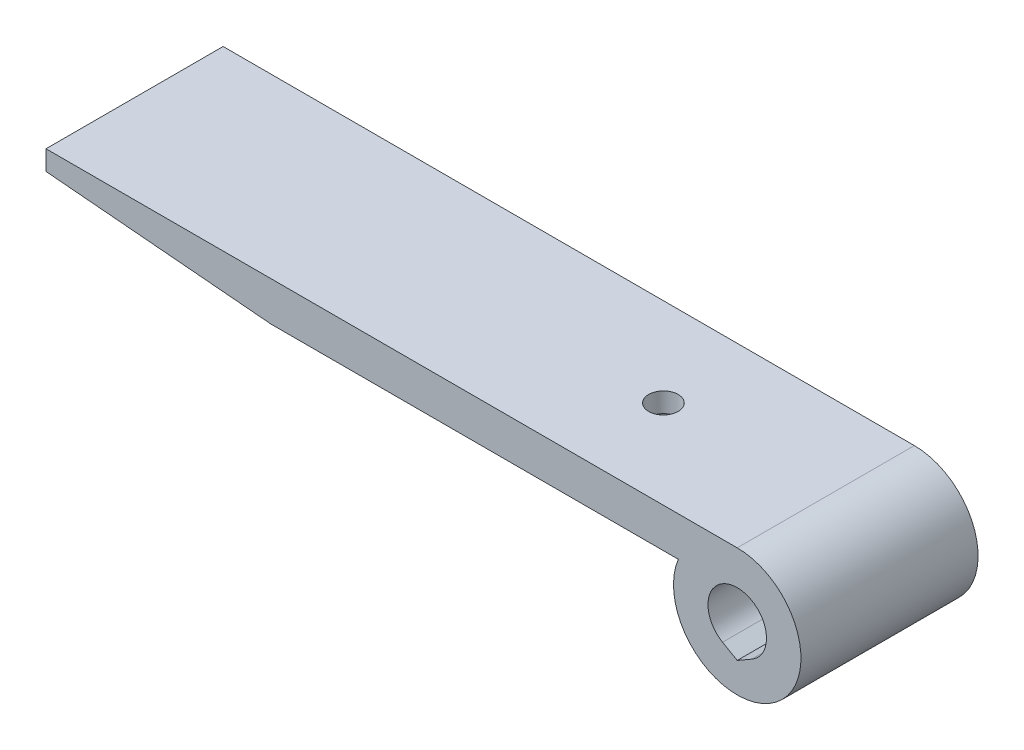
SolidWorks part; units mm, degrees
ref_plane "Front Plane" through (0, 0, 0) normal (0, 0, 1) x (1, 0, 0)
ref_plane "Top Plane" through (0, 0, 0) normal (0, 1, 0) x (1, 0, 0)
ref_plane "Right Plane" through (0, 0, 0) normal (1, 0, 0) x (0, 0, -1)
sketch "Sketch1" plane through (0, 0, 0) normal (0, 0, 1) x (1, 0, 0)
  line L0 (0, 6.475) -> (-70.2404, 6.475)
  line L1 (-70.2404, 6.475) -> (-70.2404, 4.475)
  line L2 (-70.2404, 4.475) -> (-4.6797, 4.475)
  line L3 (-70.2404, 4.475) -> (-47.3803, 2.475)
  line L4 (-47.3803, 2.475) -> (-5.9833, 2.475)
  line L5 (1.4875, -2.5764) -> (0, -3.4352)
  line L6 (0, -3.4352) -> (-1.4875, -2.5764)
  arc A0 (1.4875, -2.5764) -> (-1.4875, -2.5764) centre (0, 0) ccw
  arc A1 (-4.6797, 4.475) -> (0, 6.475) centre (0, 0) ccw
  dimension "D1" = 5.95
  dimension "D2" = 3.5
  dimension "D3" = 70.2404
  dimension "D4" = 2
  dimension "D5" = 2
  dimension "D6" = 5
  dimension "D7" = 30
extrude "main" add sketch "Sketch1" along normal mid plane 18 contours L2 A1 L0 L1 A0 region at (3.1662, -4.7361, 0)
extrude "rib" add sketch "Sketch1<4>" along normal blind 2 from surface contours A1 L2 L3 L4 region at (-32.5217, 3.5504, 0) starting at face at (0, -1.0122, -9)
sketch "Sketch1<4>" plane through (0, 0, 0) normal (0, 0, 1) x (1, 0, 0) same geometry as "Sketch1"
extrude "Boss-Extrude1" add sketch "Sketch1<5>" against normal blind 2 from surface contours A1 L2 L3 L4 region at (-32.5217, 3.5504, 0) starting at face at (0, -1.0122, 9)
sketch "Sketch1<5>" plane through (0, 0, 0) normal (0, 0, 1) x (1, 0, 0) same geometry as "Sketch1"
sketch "Sketch2" plane through (0, 4.475, 0) normal (0, -1, 0) x (1, 0, 0)
  circle A0 centre (-16.5, 0) radius 1.5
  circle A1 centre (-16.5, 0) radius 4.05
  circle A2 centre (-16.5, 0) radius 6.95
  line M1 (-4.6797, 7) -> (-70.2404, 7)
  line M3 (-70.2404, -7) -> (-4.6797, -7)
  dimension "D2" = 3
  dimension "D3" = 8.1
  dimension "D4" = 13.9
  dimension "D1" = 16.5
extrude "Cut-Extrude1" cut sketch "Sketch2" against normal through all contours A0
extrude "Boss-Extrude2" add sketch "Sketch2<4>" along normal blind 4 contours A2 A1 M1 M3 region at (-23.2534, 4.475, 0)
sketch "Sketch2<4>" plane through (0, 4.475, 0) normal (0, -1, 0) x (1, 0, 0) same geometry as "Sketch2"
equation "\"lever_length\"=70.2404"
equation "\"D3@Sketch1\"=\"lever_length\""
equation "\"magnet_separation\"= 16.5"
equation "\"D1@Sketch2\"=\"magnet_separation\""
